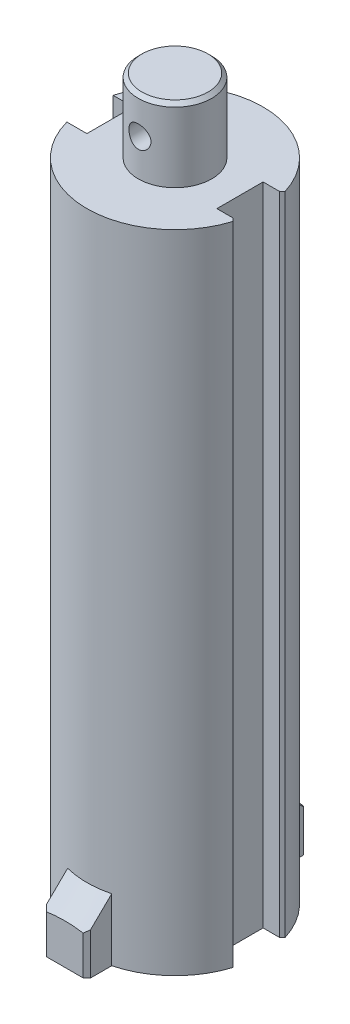
SolidWorks part; units mm, degrees
ref_plane "前视基准面" through (0, 0, 0) normal (0, 0, 1) x (1, 0, 0)
ref_plane "上视基准面" through (0, 0, 0) normal (0, 1, 0) x (1, 0, 0)
ref_plane "右视基准面" through (0, 0, 0) normal (1, 0, 0) x (0, 0, -1)
sketch "草图1" plane through (0, 0, 0) normal (0, 1, 0) x (1, 0, 0)
  circle A0 centre (0, 0) radius 12
  dimension "D1" = 24
extrude "凸台-拉伸1" add sketch "草图1" along normal blind 88
sketch "草图3" plane through (0, 88, 0) normal (0, 1, 0) x (1, 0, 0)
  circle A0 centre (0, 0) radius 7.5
  dimension "D1" = 15
extrude "切除-拉伸2" cut sketch "草图3" against normal through all
sketch "草图11" plane through (0, 0, 0) normal (0, -1, 0) x (1, 0, 0)
  line L0 (0, 0) -> (0, 12) construction
  line L1 (-17.9046, 0) -> (18.5374, 0) construction
  line L2 (-3, 15) -> (3, 15)
  line L3 (-3, 15) -> (-3, 9)
  line L4 (-3, 9) -> (3, 9)
  line L5 (3, 15) -> (3, 9)
  line L6 (-3, 15) -> (3, 9) construction
  line L7 (-3, 9) -> (3, 15) construction
  line L10 (-3, -9) -> (3, -9)
  line L11 (3, -15) -> (3, -9)
  line L12 (-3, -15) -> (3, -15)
  line L13 (-3, -15) -> (-3, -9)
  circle A1 centre (0, 0) radius 12 construction
  dimension "D1" = 6
  dimension "D2" = 6
  dimension "D3" = 12
extrude "凸台-拉伸2" add sketch "草图11" against normal blind 5
sketch "草图12" plane through (0, 0, 0) normal (0, -1, 0) x (1, 0, 0)
  circle A0 centre (0, 0) radius 7.5 construction
  circle A1 centre (0, 0) radius 7.5
curve "螺旋线/涡状线1" pitch 5 height 25 radius 7.5 centre (0, 0, 0) axis (0, 1, 0) start towards (0, 0, -1)
ref_plane "基准面1" through (0, 0, -7.5) normal (-0.9944, 0.1055, 0) x (0, 0, -1)
sketch "草图13" plane through (0, 0, -7.5) normal (-0.9944, 0.1055, 0) x (0, 0, -1)
  line L1 (-1.9, -1.2) -> (1.9, -1.2)
  line L2 (-1.9, -1.2) -> (-1.9, 1.2)
  line L3 (-1.9, 1.2) -> (1.9, 1.2)
  line L4 (1.9, -1.2) -> (1.9, 1.2)
  line L5 (-1.9, -1.2) -> (1.9, 1.2) construction
  line L6 (-1.9, 1.2) -> (1.9, -1.2) construction
  point P0 (0, 0)
  point P1 (0, 0)
  dimension "D1" = 2.4
  dimension "D2" = 3.8
sweep "扫描1" add profiles "草图13" path "螺旋线/涡状线1"
sketch "草图8" plane through (0, 0, 0) normal (1, 0, 0) x (0, 0, -1)
  line L0 (12, 88) -> (-12, 88) construction
  line L1 (16.7377, 88) -> (-21.577, 88)
  line L2 (16.7377, 88) -> (16.7377, 112.1834)
  line L3 (16.7377, 112.1834) -> (-21.577, 112.1834)
  line L4 (-21.577, 88) -> (-21.577, 112.1834)
  line L5 (-19.9763, 0) -> (17.2217, 0)
  line L6 (-19.9763, 0) -> (-19.9763, -6.9668)
  line L7 (-19.9763, -6.9668) -> (17.2217, -6.9668)
  line L8 (17.2217, 0) -> (17.2217, -6.9668)
extrude "切除-拉伸4" cut sketch "草图8" against normal through all and the other way through all
sketch "草图14" plane through (0, 88, 0) normal (0, 1, 0) x (1, 0, 0)
  circle A0 centre (0, 0) radius 9
extrude "凸台-拉伸3" add sketch "草图14" against normal blind 4
sketch "草图15" plane through (0, 88, 0) normal (0, 1, 0) x (1, 0, 0)
  circle A0 centre (0, 0) radius 5
  dimension "D1" = 10
extrude "凸台-拉伸4" add sketch "草图15" along normal blind 10
sketch "草图16" plane through (0, 0, 0) normal (0, 0, 1) x (1, 0, 0)
  line L0 (0, 98) -> (0, 93) construction
  line L1 (5, 98) -> (-5, 98) construction
  circle A0 centre (0, 93) radius 1.5
  dimension "D1" = 3
  dimension "D2" = 5
extrude "切除-拉伸5" cut sketch "草图16" against normal through all and the other way through all
sketch "草图2" plane through (0, 88, 0) normal (0, 1, 0) x (1, 0, 0)
  line L0 (0, 0) -> (-12, 0) construction
  line L1 (0, 12) -> (0, -12) construction
  line L2 (-15.15, -3.15) -> (-8.85, -3.15)
  line L3 (-15.15, -3.15) -> (-15.15, 3.15)
  line L4 (-15.15, 3.15) -> (-8.85, 3.15)
  line L5 (-8.85, -3.15) -> (-8.85, 3.15)
  line L6 (-15.15, -3.15) -> (-8.85, 3.15) construction
  line L7 (-15.15, 3.15) -> (-8.85, -3.15) construction
  line L12 (15.15, 3.15) -> (8.85, 3.15)
  line L13 (8.85, -3.15) -> (8.85, 3.15)
  line L14 (15.15, -3.15) -> (8.85, -3.15)
  line L15 (15.15, -3.15) -> (15.15, 3.15)
  circle A1 centre (0, 0) radius 12 construction
  point P4 (-12, 0)
  dimension "D1" = 12
  dimension "D2" = 6.3
  dimension "D3" = 6.3
extrude "切除-拉伸1" cut sketch "草图2" against normal blind 100
chamfer "倒角1" distance 0.5 angle 45 7 edges at (0, 98, 5) (11.5792, 44, 3.15) (11.5792, 44, -3.15) (-3, 2.5, 15) (3, 2.5, 15) (-3, 2.5, -15) (3, 2.5, -15) first distance on face at (0.2714, 91.5248, -4.9926) first distance on face at (10.2146, 44, 3.15) first distance on face at (10.2146, 44, -3.15) first distance on face at (-3, 2.5, 13.3095) first distance on face at (0, 2.5, 15) first distance on face at (0, 2.5, -15) first distance on face at (3, 2.5, -13.3095)
chamfer "倒角2" distance 3.5 angle 45 2 edges at (0, 5, 12) (0, 5, -12)
